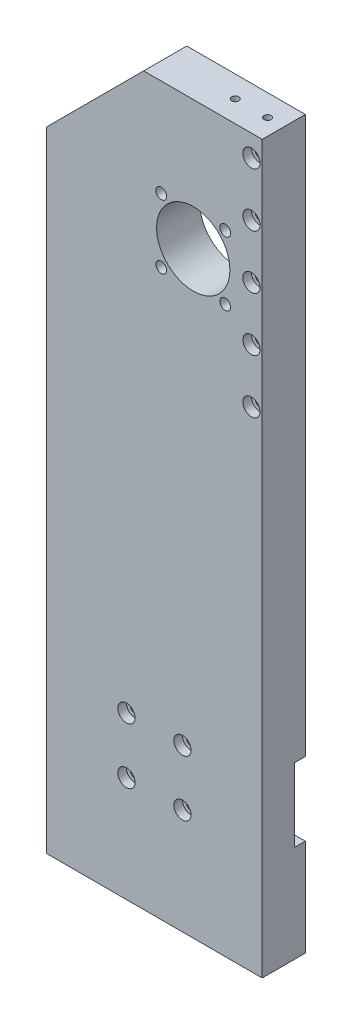
SolidWorks part; units mm, degrees
ref_plane "Front Plane" through (0, 0, 0) normal (0, 0, 1) x (1, 0, 0)
ref_plane "Top Plane" through (0, 0, 0) normal (0, 1, 0) x (1, 0, 0)
ref_plane "Right Plane" through (0, 0, 0) normal (1, 0, 0) x (0, 0, -1)
sketch "Sketch1" plane through (0, 0, 0) normal (0, 0, 1) x (1, 0, 0)
  line L0 (65.7045, 560.5004) -> (50.8553, 575.3496) construction
  line L1 (65.7045, 560.5004) -> (44.7045, 560.5004) construction
  line L2 (65.7045, 560.5004) -> (65.7045, 581.5004) construction
  line L3 (47.7045, 545.8558) -> (47.7045, 439.2537) construction
  line L4 (7.7288, 345.5004) -> (63.5732, 345.5004) construction
  line L5 (97.7045, 283.5004) -> (-2.2955, 283.5004)
  line L6 (97.7045, 283.5004) -> (97.7045, 620.5004)
  line L7 (97.7045, 620.5004) -> (-2.2955, 620.5004)
  line L8 (-2.2955, 283.5004) -> (-2.2955, 620.5004)
  line L9 (97.7045, 283.5004) -> (-2.2955, 620.5004) construction
  line L10 (97.7045, 620.5004) -> (-2.2955, 283.5004) construction
  circle A0 centre (65.7045, 560.5004) radius 17
  circle A1 centre (65.7045, 560.5004) radius 21 construction
  circle A2 centre (80.5538, 575.3496) radius 2.5
  circle A3 centre (80.5538, 545.6511) radius 2.5
  circle A4 centre (50.8553, 545.6511) radius 2.5
  circle A5 centre (50.8553, 575.3496) radius 2.5
  circle A6 centre (34.7045, 358.5004) radius 2
  circle A7 centre (60.7045, 358.5004) radius 2
  circle A8 centre (34.7045, 332.5004) radius 2
  circle A9 centre (60.7045, 332.5004) radius 2
  point P5 (50.8553, 575.3496)
  point P6 (80.5538, 575.3496)
  point P7 (80.5538, 545.6511)
  point P8 (50.8553, 545.6511)
  point P19 (47.7045, 452.0004)
  point P35 (34.7045, 358.5004)
  point P36 (60.7045, 358.5004)
  point P37 (60.7045, 332.5004)
  point P38 (34.7045, 332.5004)
  dimension "D2" = 5
  dimension "D3" = 34
  dimension "D4" = 42
  dimension "D10" = 4
  dimension "D1" = 45
  dimension "D5" = 337
  dimension "D6" = 100
  dimension "D7" = 60
  dimension "D8" = 75
  dimension "D9" = 13
  dimension "D11" = 62
  dimension "D12" = 32
extrude "Boss-Extrude1" add sketch "Sketch1" along normal blind 20
chamfer "Chamfer1" distance 45 angle 45 1 edges at (-2.2955, 620.5004, 10)
sketch "Sketch2" plane through (0, 0, 0) normal (0, 0, 1) x (1, 0, 0)
  line L0 (60.7045, 358.5004) -> (34.7045, 332.5004) construction
  line L1 (34.7045, 358.5004) -> (60.7045, 332.5004) construction
  line L3 (97.7045, 328.5004) -> (-2.2955, 328.5004)
  line L4 (97.7045, 328.5004) -> (97.7045, 362.5004)
  line L5 (97.7045, 362.5004) -> (-2.2955, 362.5004)
  line L6 (-2.2955, 328.5004) -> (-2.2955, 362.5004)
  line L7 (97.7045, 328.5004) -> (-2.2955, 362.5004) construction
  line L8 (97.7045, 362.5004) -> (-2.2955, 328.5004) construction
  point P8 (47.7045, 345.5004)
  point P9 (47.7045, 345.5004)
  dimension "D1" = 100
  dimension "D2" = 34
extrude "Cut-Extrude1" cut sketch "Sketch2" along normal blind 5
sketch "Sketch3" plane through (0, 0, 20) normal (0, 0, 1) x (1, 0, 0)
  line L0 (92.7045, 620.5004) -> (92.7045, 500.5004) construction
  line L1 (97.7045, 620.5004) -> (87.7045, 620.5004) construction
  line L2 (97.7045, 620.5004) -> (97.7045, 500.5004) construction
  line L3 (97.7045, 500.5004) -> (87.7045, 500.5004) construction
  line L4 (87.7045, 620.5004) -> (87.7045, 500.5004) construction
  line L5 (97.7045, 560.5004) -> (87.7045, 560.5004) construction
  point P9 (92.7045, 535.5004)
  point P10 (92.7045, 585.5004)
  point P11 (92.7045, 560.5004)
  point P12 (92.7045, 610.5004)
  point P13 (92.7045, 510.5004)
  dimension "D1" = 10
  dimension "D2" = 120
  dimension "D3" = 3
hole_wizard "CBORE for M4 SHCS1" positions "Sketch5" profile "Sketch6" counterbore size "M4" standard "ANSI Metric" end condition through all
sketch "Sketch5" plane through (0, 0, 20) normal (0, 0, 1) x (1, 0, 0)
  point P0 (92.7045, 610.5004)
  point P5 (92.7045, 585.5004)
  point P8 (92.7045, 560.5004)
  point P11 (92.7045, 535.5004)
  point P14 (92.7045, 510.5004)
sketch "Sketch6" plane through (92.7045, 610.5004, 20) normal (1, 0, 0) x (0, -1, 0)
  line L0 (0, 0) -> (0, 20)
  line L1 (0, 20) -> (2.25, 20)
  line L3 (2.25, 20) -> (2.25, 4)
  line L4 (2.25, 4) -> (4, 4)
  line L5 (4, 4) -> (4, 0)
  line L7 (4, 0) -> (0, 0)
  line L11 (0, -6.35) -> (0, 107.95) construction
  dimension "Thru Hole Dia." = 4.5
  dimension "Thru Hole Depth" = 20
  dimension "C'Bore Dia." = 8
  dimension "C'Bore Depth" = 4
hole_wizard "CBORE for M4 SHCS2" positions "3DSketch2" profile "Sketch10" counterbore size "M4" standard "ANSI Metric" end condition through all
sketch3d "3DSketch2"
  line L0 (34.7045, 358.5004, 20) -> (34.7045, 358.5004, 5) construction
  line L1 (60.7045, 358.5004, 20) -> (60.7045, 358.5004, 5) construction
  line L2 (34.7045, 332.5004, 20) -> (34.7045, 332.5004, 5) construction
  line L3 (60.7045, 332.5004, 20) -> (60.7045, 332.5004, 5) construction
  point P0 (34.7045, 358.5004, 20)
  point P4 (60.7045, 358.5004, 20)
  point P8 (34.7045, 332.5004, 20)
  point P12 (60.7045, 332.5004, 20)
sketch "Sketch10" plane through (34.7045, 358.5004, 20) normal (1, 0, 0) x (0, -1, 0)
  line L0 (0, 0) -> (0, 20)
  line L1 (0, 20) -> (2.25, 20)
  line L3 (2.25, 20) -> (2.25, 4)
  line L4 (2.25, 4) -> (4, 4)
  line L5 (4, 4) -> (4, 0)
  line L7 (4, 0) -> (0, 0)
  line L11 (0, -6.35) -> (0, 107.95) construction
  dimension "Thru Hole Dia." = 4.5
  dimension "Thru Hole Depth" = 20
  dimension "C'Bore Dia." = 8
  dimension "C'Bore Depth" = 4
sketch "Sketch11" plane through (0, 283.5004, 0) normal (0, -1, 0) x (1, 0, 0)
  line L0 (-2.2955, 10) -> (97.7045, 10) construction
  line L1 (-2.2955, 20) -> (-2.2955, 0) construction
  line L2 (97.7045, 20) -> (97.7045, 0) construction
  line L3 (47.7045, 20) -> (47.7045, 0) construction
  line L4 (-2.2955, 20) -> (97.7045, 20) construction
  line L5 (-2.2955, 0) -> (97.7045, 0) construction
  point P12 (67.7045, 10)
  point P13 (87.7045, 10)
  point P14 (47.7045, 10)
  point P15 (7.7045, 10)
  point P16 (27.7045, 10)
  dimension "D1" = 20
  dimension "D2" = 40
hole_wizard "M4 Tapped Hole1" positions "3DSketch3" profile "Sketch12" tap size "M4" standard "ISO"
sketch3d "3DSketch3"
  point P0 (7.7045, 283.5004, 10)
  point P3 (27.7045, 283.5004, 10)
  point P6 (67.7045, 283.5004, 10)
  point P9 (87.7045, 283.5004, 10)
sketch "Sketch12" plane through (7.7045, 283.5004, 10) normal (1, 0, 0) x (0, 0, -1)
  line L0 (0, 0) -> (0, 17.0914)
  line L1 (0, 17.0914) -> (1.65, 16.1)
  line L2 (1.65, 16.1) -> (1.65, 0)
  line L5 (1.65, 0) -> (0, 0)
  line L10 (0, 17.0914) -> (-1.65, 16.1) construction
  line L11 (0, -6.35) -> (0, 107.95) construction
  dimension "Tap Drill Dia." = 3.3
  dimension "Tap Drill Depth" = 16.1
  dimension "Drill Angle" = 118
sketch "Sketch13" plane through (0, 620.5004, 0) normal (0, 1, 0) x (1, 0, 0)
  point P0 (90.2045, -10)
  point P1 (75.2045, -10)
hole_wizard "M4 Tapped Hole2" positions "3DSketch4" profile "Sketch14" tap size "M4" standard "ISO"
sketch3d "3DSketch4"
  line L0 (90.2045, 625.5004, 10) -> (90.2045, 620.5004, 10) construction
  line L1 (75.2045, 625.5004, 10) -> (75.2045, 620.5004, 10) construction
  point P0 (90.2045, 625.5004, 10)
  point P4 (75.2045, 625.5004, 10)
sketch "Sketch14" plane through (90.2045, 625.5004, 10) normal (1, 0, 0) x (0, 0, 1)
  line L0 (0, 0) -> (0, 16.0914)
  line L1 (0, 16.0914) -> (1.65, 15.1)
  line L2 (1.65, 15.1) -> (1.65, 0)
  line L5 (1.65, 0) -> (0, 0)
  line L10 (0, 16.0914) -> (-1.65, 15.1) construction
  line L11 (0, -6.35) -> (0, 107.95) construction
  dimension "Tap Drill Dia." = 3.3
  dimension "Tap Drill Depth" = 15.1
  dimension "Drill Angle" = 118
